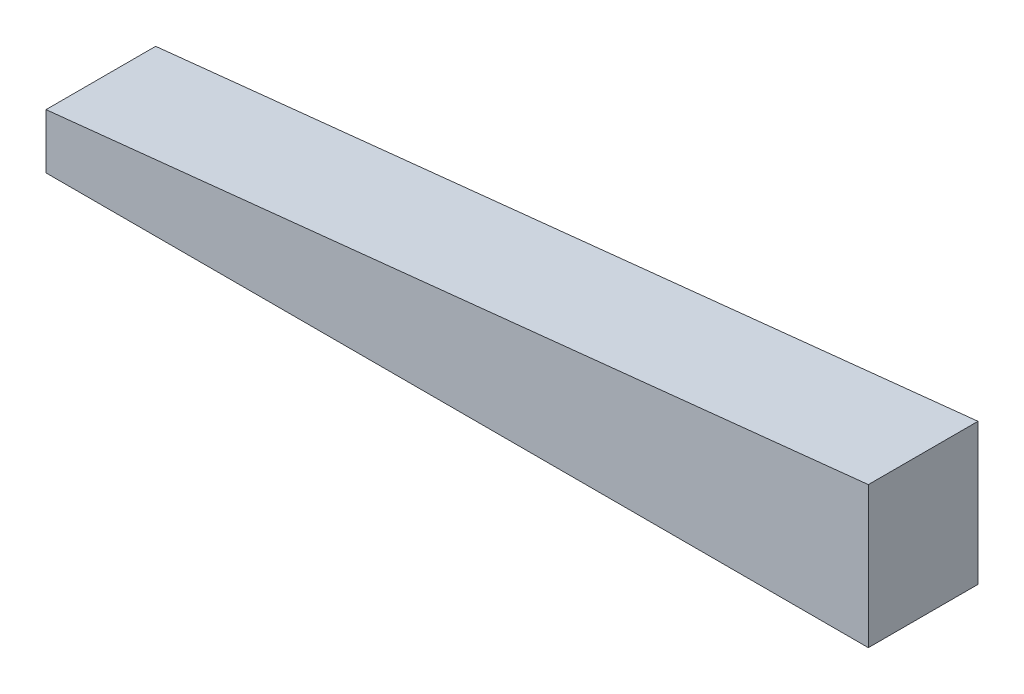
SolidWorks part; units mm, degrees
ref_plane "Front Plane" through (0, 0, 0) normal (0, 0, 1) x (1, 0, 0)
ref_plane "Top Plane" through (0, 0, 0) normal (0, 1, 0) x (1, 0, 0)
ref_plane "Right Plane" through (0, 0, 0) normal (1, 0, 0) x (0, 0, -1)
sketch "Sketch1" plane through (0, 0, 0) normal (0, 1, 0) x (1, 0, 0)
  line L1 (-75, -10) -> (75, -10)
  line L2 (-75, -10) -> (-75, 10)
  line L3 (-75, 10) -> (75, 10)
  line L4 (75, -10) -> (75, 10)
  line L5 (-75, -10) -> (75, 10) construction
  line L6 (-75, 10) -> (75, -10) construction
  point P0 (0, 0)
  dimension "D1" = 20
  dimension "D2" = 150
extrude "Boss-Extrude1" add sketch "Sketch1" along normal blind 10
sketch "Sketch2" plane through (0, 0, 0) normal (0, 0, 1) x (1, 0, 0)
  line L0 (-75, 10) -> (75, 10)
  line L1 (75, 10) -> (75, 25.7656)
  line L2 (75, 25.7656) -> (-75, 10)
  dimension "D1" = 6
extrude "Boss-Extrude2" add sketch "Sketch2" along normal mid plane 20
